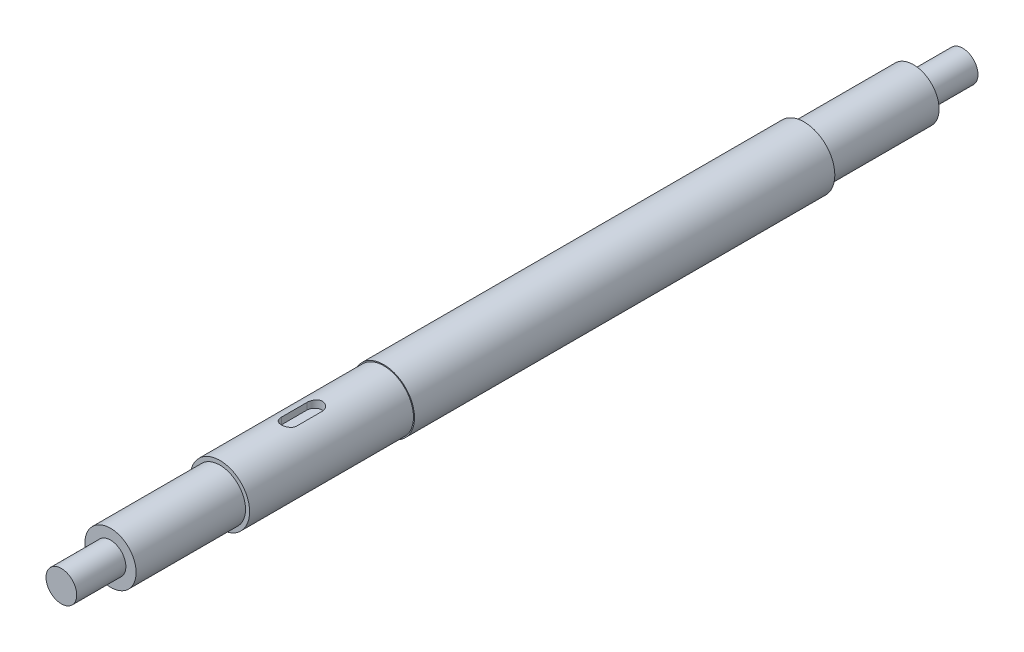
SolidWorks part; units mm, degrees
material "Alloy Steel"
ref_plane "Front Plane" through (0, 0, 0) normal (0, 0, 1) x (1, 0, 0)
ref_plane "Top Plane" through (0, 0, 0) normal (0, 1, 0) x (1, 0, 0)
ref_plane "Right Plane" through (0, 0, 0) normal (1, 0, 0) x (0, 0, -1)
sketch "Sketch1" plane through (0, 0, 0) normal (0, 0, 1) x (1, 0, 0)
  circle A0 centre (0, 0) radius 9.525
  dimension "D1" = 19.05
extrude "Boss-Extrude1" add sketch "Sketch1" along normal mid plane 279.4
ref_plane "Plane1" through (0, 0, 90.551) normal (0, 0, 1) x (1, 0, 0)
sketch "Sketch3" plane through (0, 0, 90.551) normal (0, 0, 1) x (1, 0, 0)
  circle A0 centre (0, 0) radius 7.9375
  circle A1 centre (0, 0) radius 9.525
  circle A2 centre (0, 0) radius 9.525
  dimension "D2" = 15.875
  dimension "D1" = 0
extrude "Cut-Extrude1" cut sketch "Sketch3" along normal up to next
mirror "Mirror1" about plane through (0, 0, 0) normal (0, 0, 1) of "Cut-Extrude1"
ref_plane "Plane2" through (0, 0, 124.46) normal (0, 0, 1) x (1, 0, 0)
sketch "Sketch4" plane through (0, 0, 124.46) normal (0, 0, 1) x (1, 0, 0)
  circle A0 centre (0, 0) radius 4.7625
  circle A1 centre (0, 0) radius 7.9375
  circle A2 centre (0, 0) radius 7.9375
  dimension "D2" = 9.525
  dimension "D1" = 0
extrude "Cut-Extrude2" cut sketch "Sketch4" along normal up to next
mirror "Mirror2" about plane through (0, 0, 0) normal (0, 0, 1) of "Cut-Extrude2"
sketch "Sketch5" plane through (0, 0, 90.551) normal (0, 0, 1) x (1, 0, 0)
  circle A0 centre (0, 0) radius 9.525 construction
  circle A1 centre (0, 0) radius 9.525
  circle A2 centre (0, 0) radius 9.2075
  dimension "D1" = 18.415
extrude "Cut-Extrude3" cut sketch "Sketch5" against normal blind 50.8
ref_plane "Plane3" through (0, 9.2075, 0) normal (0, 1, 0) x (1, 0, 0)
sketch "Sketch6" plane through (0, 9.2075, 0) normal (0, 1, 0) x (1, 0, 0)
  line L0 (-9.525, -39.751) -> (9.525, -39.751) construction
  line L1 (-9.2075, -90.551) -> (9.2075, -90.551) construction
  line L2 (-9.525, -39.751) -> (9.525, -39.751)
  line L3 (-9.2075, -90.551) -> (9.2075, -90.551)
  line L4 (0, -90.551) -> (0, -39.751) construction
  line L5 (-9.2075, -65.151) -> (9.2075, -65.151) construction
  line L6 (-9.2075, -39.751) -> (-9.2075, -90.551) construction
  line L7 (9.2075, -90.551) -> (9.2075, -39.751) construction
  line L8 (0, -69.1197) -> (0, -61.1822) construction
  line L9 (-2.3813, -69.1197) -> (-2.3813, -61.1822)
  line L10 (2.3813, -69.1197) -> (2.3812, -61.1822)
  line L11 (0, -58.801) -> (-5.2744, -58.801) construction
  line L12 (0, -71.501) -> (-5.6689, -71.501) construction
  arc A0 (-2.3813, -69.1197) -> (2.3813, -69.1197) centre (0, -69.1197) ccw
  arc A1 (2.3812, -61.1822) -> (-2.3813, -61.1822) centre (0, -61.1822) ccw
  point P14 (0, -65.151)
  dimension "D1" = 4.7625
  dimension "D2" = 12.7
extrude "Cut-Extrude4" cut sketch "Sketch6" against normal blind 2.3812 contours L10 A1 L9 A0 region at (0, 9.2075, 65.151)
